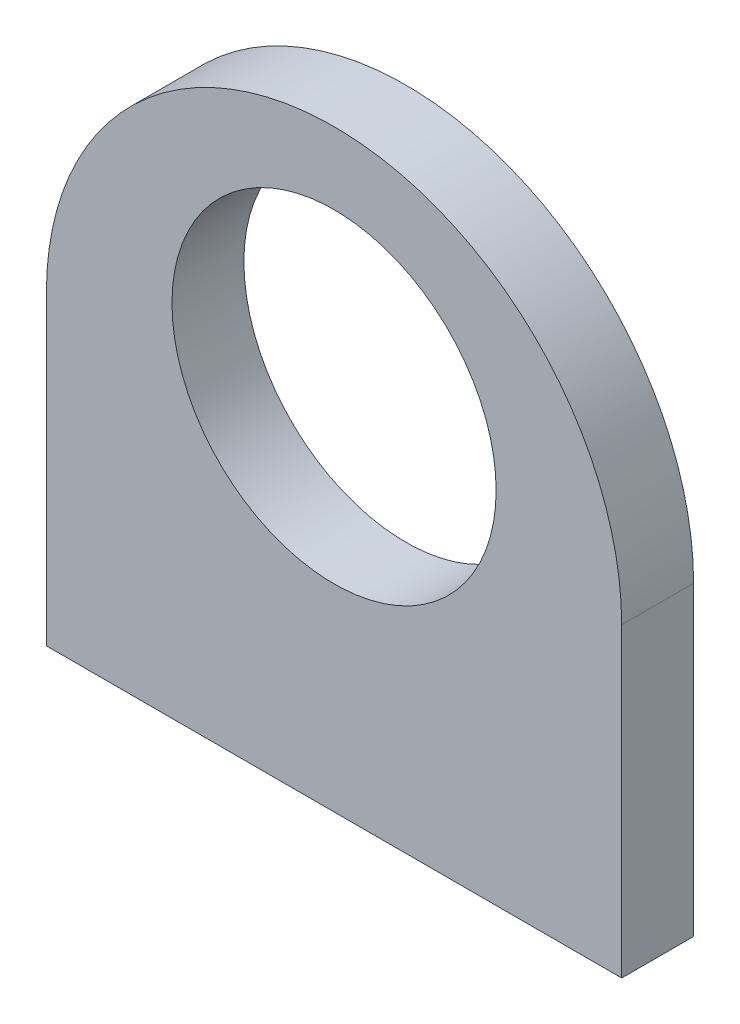
SolidWorks part; units mm, degrees
material "6061 Alloy"
ref_plane "Front" through (0, 0, 0) normal (0, 0, 1) x (1, 0, 0)
ref_plane "Top" through (0, 0, 0) normal (0, 1, 0) x (1, 0, 0)
ref_plane "Right" through (0, 0, 0) normal (1, 0, 0) x (0, 0, -1)
sketch "Sketch1" plane through (0, 0, 0) normal (0, 0, 1) x (1, 0, 0)
  line L0 (50.8, 31.75) -> (0, 31.75) construction
  line L1 (0, 0) -> (50.8, 0)
  line L2 (0, 0) -> (0, 27.0129)
  line L4 (50.8, 0) -> (50.8, 27.0129)
  circle A0 centre (25.4, 31.75) radius 14.3129
  arc A1 (50.8, 27.0129) -> (0, 27.0129) centre (25.4, 27.0129) ccw
  point P10 (25.4, 31.75)
  dimension "D3" = 28.6258
  dimension "D4" = 6.35
  dimension "D1" = 50.8
  dimension "D2" = 31.75
extrude "Boss-Extrude1" add sketch "Sketch1" along normal blind 6.35
